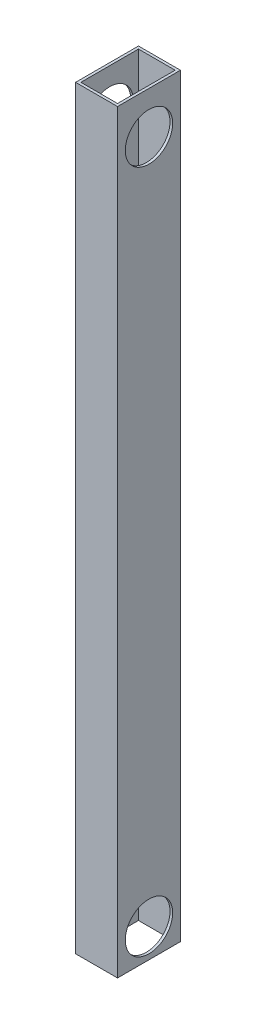
SolidWorks part; units mm, degrees
ref_plane "Front Plane" through (0, 0, 0) normal (0, 0, 1) x (1, 0, 0)
ref_plane "Top Plane" through (0, 0, 0) normal (0, 1, 0) x (1, 0, 0)
ref_plane "Right Plane" through (0, 0, 0) normal (1, 0, 0) x (0, 0, -1)
sketch "Sketch1" plane through (0, 0, 0) normal (0, 1, 0) x (1, 0, 0)
  line L1 (0, 0) -> (25.4, 0)
  line L2 (0, 0) -> (0, 38.1)
  line L3 (0, 38.1) -> (25.4, 38.1)
  line L4 (25.4, 0) -> (25.4, 38.1)
  dimension "D1" = 38.1
  dimension "D2" = 25.4
extrude "Extrude-Thin1" add sketch "Sketch1" along normal blind 457.2 thin thin type one direction reverse wall 1.5875
sketch "Sketch2" plane through (25.4, 0, 0) normal (1, 0, 0) x (0, 0, -1)
  line L0 (0, 0) -> (38.1, 0) construction
  line L1 (0, 457.2) -> (0, 0) construction
  line L2 (0, 457.2) -> (38.1, 457.2) construction
  circle A0 centre (19.05, 17.526) radius 14.351
  circle A1 centre (19.05, 431.8) radius 14.351
  dimension "D1" = 17.526
  dimension "D2" = 28.702
  dimension "D4" = 25.4
  dimension "D5" = 28.702
  dimension "D6" = 19.05
  dimension "D3" = 19.05
extrude "Cut-Extrude1" cut sketch "Sketch2" against normal through all both and the other way through all
